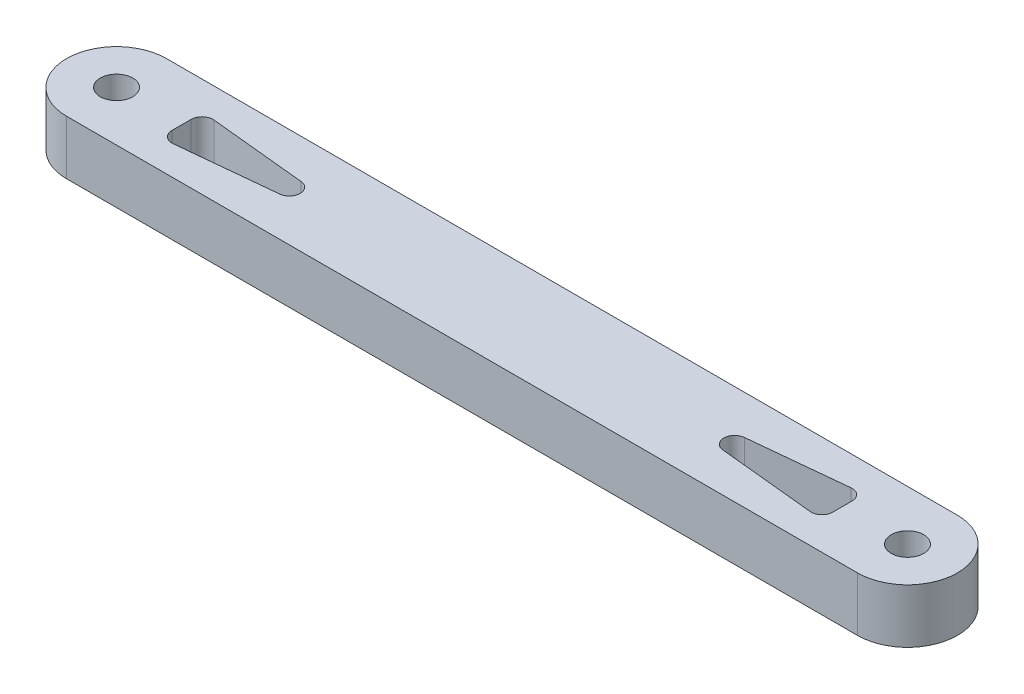
SolidWorks part; units mm, degrees
ref_plane "Front Plane" through (0, 0, 0) normal (0, 0, 1) x (1, 0, 0)
ref_plane "Top Plane" through (0, 0, 0) normal (0, 1, 0) x (1, 0, 0)
ref_plane "Right Plane" through (0, 0, 0) normal (1, 0, 0) x (0, 0, -1)
sketch "Sketch1" plane through (0, 0, 0) normal (0, 1, 0) x (1, 0, 0)
  line L0 (0, 0) -> (73, 0) construction
  line L1 (0, 0) -> (73, 0) construction
  line L2 (0, 4.6106) -> (73, 4.6106)
  line L3 (0, -4.6106) -> (73, -4.6106)
  circle A0 centre (0, 0) radius 1.5
  circle A1 centre (73, 0) radius 1.5
  arc A2 (0, 4.6106) -> (0, -4.6106) centre (0, 0) ccw
  arc A3 (73, -4.6106) -> (73, 4.6106) centre (73, 0) ccw
  point P5 (36.5, 0)
  dimension "D1" = 73
extrude "Boss-Extrude1" add sketch "Sketch1" along normal blind 5 contours L3 A3 L2 A2 A0 A1 | L3 A3 L2 A2 | A0 | A1 region at (36.5, 0, 0)
sketch "Sketch3" plane through (0, 5, 0) normal (0, 1, 0) x (1, 0, 0)
  line L0 (36.5, 4.6106) -> (36.5, -4.6106) construction
  line L1 (0, 4.6106) -> (73, 4.6106) construction
  line L2 (0, -4.6106) -> (73, -4.6106) construction
  line L3 (0, 0) -> (6, 0) construction
  line L4 (6, 2) -> (6, -2)
  line L5 (6, 0) -> (26, 0) construction
  line L6 (6, -2) -> (26, 0)
  line L7 (6, 2) -> (26, 0)
  line L8 (67, 2) -> (67, -2)
  line L9 (67, -2) -> (47, 0)
  line L10 (67, 2) -> (47, 0)
  dimension "D1" = 6
  dimension "D2" = 2
  dimension "D3" = 20
extrude "Cut-Extrude2" cut sketch "Sketch3" against normal blind 17
fillet "Fillet1" radius 1 6 edges at (67, 2.5, 2) (67, 2.5, -2) (47, 2.5, 0) (26, 2.5, 0) (6, 2.5, 2) (6, 2.5, -2)
